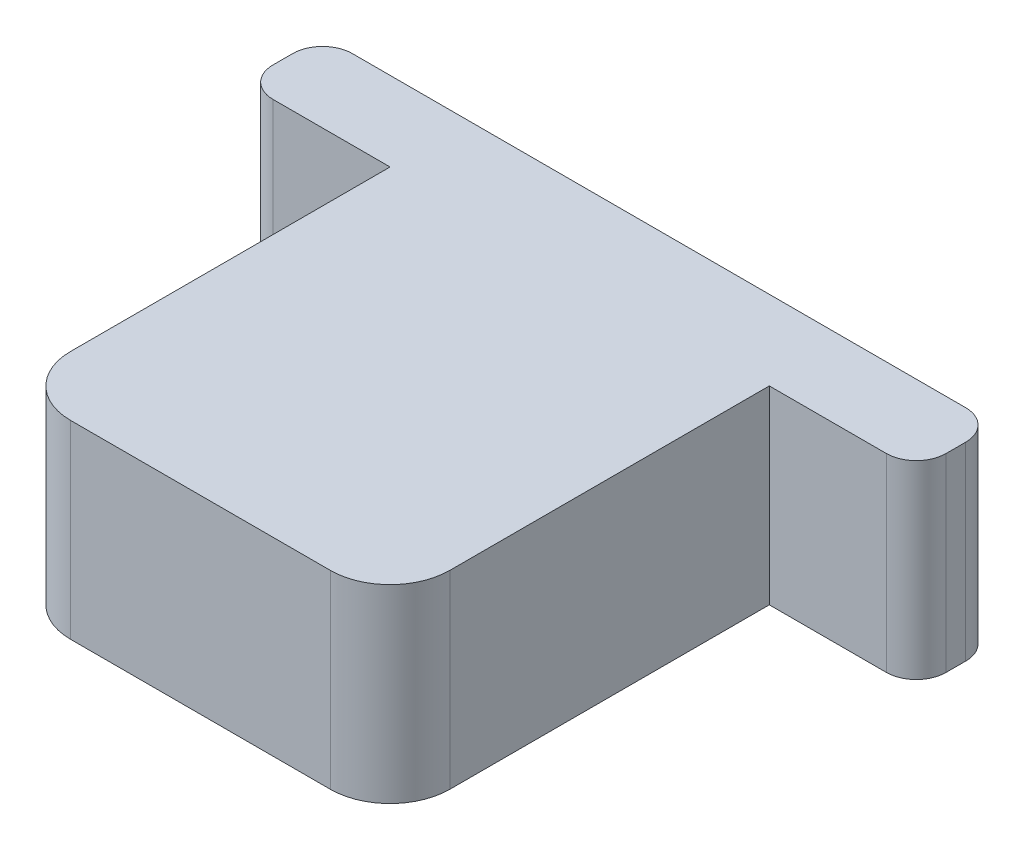
SolidWorks part; units mm, degrees
material "Beech"
ref_plane "Front Plane" through (0, 0, 0) normal (0, 0, 1) x (1, 0, 0)
ref_plane "Top Plane" through (0, 0, 0) normal (0, 1, 0) x (1, 0, 0)
ref_plane "Right Plane" through (0, 0, 0) normal (1, 0, 0) x (0, 0, -1)
sketch "Sketch1" plane through (0, 0, 0) normal (0, 1, 0) x (1, 0, 0)
  line L0 (0, 0) -> (6.35, 0)
  line L1 (0, 0) -> (0, 6.35)
  line L2 (6.35, 0) -> (6.35, 6.35)
  line L4 (-2.46, 7.6787) -> (-2.46, 6.35)
  line L5 (-2.46, 7.6787) -> (8.81, 7.6787)
  line L6 (-2.46, 6.35) -> (0, 6.35)
  line L7 (8.81, 7.6787) -> (8.81, 6.35)
  line L8 (6.35, 6.35) -> (8.81, 6.35)
  dimension "D1" = 6.35
  dimension "D2" = 6.35
  dimension "D3" = 11.27
  dimension "D4" = 1.3287
extrude "Boss-Extrude1" add sketch "Sketch1" along normal blind 3.175
fillet "Fillet1" radius 1 2 edges at (0, 1.5875, 0) (6.35, 1.5875, 0)
fillet "Fillet2" radius 0.5 4 edges at (-2.46, 1.5875, -6.35) (-2.46, 1.5875, -7.6787) (8.81, 1.5875, -7.6787) (8.81, 1.5875, -6.35)
equation "\"CageLeftBottomEdge\"=22.11mm"
equation "\"CageLeftTopEdge\"=22.11mm"
equation "\"CageRightBottomEdge\"=21.63mm"
equation "\"CageRightTopEdge\"=21.63mm"
equation "\"CageHeight\"=86.04mm"
equation "\"CageLength\"=73.76mm"
equation "\"CageTopScrewClearance\"=10mm"
equation "\"CageBottomScrewClearance\"=25mm"
equation "\"CageLeftTopDepth\"= 11.65mm"
equation "\"CageLeftBottomDepth\"=11.11mm"
equation "\"CageLeftTopHeight\"=8.56175mm"
equation "\"CageLeftBottomHeight\"=16mm"
equation "\"CageRightTopDepth\"= 11.05mm"
equation "\"CageRightBottomDepth\"=10.58mm"
equation "\"CageRightTopHeight\"=9.6mm"
equation "\"CageRightBottomHeight\"=15.49mm"
equation "\"CageLeftTopChannelDepth\"=2.41908mm"
equation "\"CageLeftBottomChannelDepth\"=2.588mm"
equation "\"CageLeftChannelHeight\"=11.7mm"
equation "\"CageRightTopChannelDepth\"=2.32mm"
equation "\"CageRightBottomChannelDepth\"=2.318mm"
equation "\"CageRightChannelHeight\"=10mm"
equation "\"CageChanRelHeight\"=23.99mm"
equation "\"CageChanRelDepth\"=5.492mm"
equation "\"CageChamberRadius\"=16.261mm"
equation "\"CageScrewDiameter\"=4.8mm"
equation "\"CageSetScrewDiameter\"=3.5mm"
equation "\"CageAxleRadius\"=6.639mm"
equation "\"CageAxleKeyHeight\"=1.619mm"
equation "\"CageAxleKeyWidth\"=2.662mm"
equation "\"CageHoseWindowWidth\"=16.29mm"
equation "\"CageHoseWindowHeight\"=26.5mm"
equation "\"CageHoseWindow-Edge\"=8.89mm"
equation "\"CageScrew-VerticalEdge\"=5.0mm"
equation "\"CageScrew-HorizontalEdge\"=7.5mm"
equation "\"CageScrew-HoseCornerScrewEdge\"=4.45mm"
equation "\"CageAxle-BottomEdge\"=56.05mm"
equation "\"CageAxle-FrontEdge\"=46.03mm"
equation "\"CageBackSetScrew-Axle\"=40mm"
equation "\"CageFrontSetScrew-Axle\"=22mm"
equation "\"CageVelocityWindow-BackEdge\"=34.8mm"
equation "\"CageVelocityWindow-BottomEdge\"=27.55mm"
equation "\"CageVelocityWindowHeight\"=22.29mm"
equation "\"CageVelocityWindowWidth\"=12.61mm"
equation "\"TriggerSlot-BottomEdge\"=6.35mm"
equation "\"TriggerSlot-FrontEdge\"=15mm"
equation "\"TriggerSlotSize\"=6.7mm"
equation "\"vigorwidth\"= 0.472441in"
equation "\"vigorflangewidth\"= 0.731102in"
equation "\"vigorflangelength\"= 0.131102in"
equation "\"vigorscrewsize\"= 0.066535in"
equation "\"vigorholeoffsetwid\"= 0.0646653in"
equation "\"vigorholeoffsetlen\"= 0.065551in"
equation "\"vigorflangedepth\"= 0.0901575in"
equation "\"vigordiscdepth\"= 0.0492126in"
equation "\"vigormotordepth\"= 1.12362in"
equation "\"vigortipdepth\"= 0.259055in"
equation "\"vigoraxlewidth\"= 0.173622in"
equation "\"vigorcutlen\"= 0.0480315in"
equation "\"vigoraxledepth\"= 0.159055in"
equation "\"TriggerRackOffset\"=.236224in"
equation "\"TriggerSlotSizeInt\"=.25in"
equation "\"MotorMountLegLength\"=.25in"
equation "\"GearOffset\"=.264907in"
equation "\"TriggerSlotSpacing\"=.25in"
equation "\"TGMGearFaceDiameter\"=24.40mm"
equation "\"TGMCylinderLength\"=15.00mm"
equation "\"TGMScrewHole-Center\"=8.70mm"
equation "\"TGMScrewHoleDiameter\"=5.04mm"
equation "\"TGMCenterHoleDiameter\"=9.50mm"
equation "\"TGMShaftCollarSideLength\"=19.00mm"
equation "\"TGMShaftCollarDockingDepth\"=7.00mm"
equation "\"whitemotordepth\"=11.27mm"
equation "\"whitemotorbackdepth\"=3.845mm"
equation "\"whitemotoraxledepth\" = 3.5mm"
equation "\"whitemotoraxleoffset\"=11.4mm"
equation "\"whitemotorwidth\"=12.07mm"
equation "\"whitemotorheight\"=16.68mm"
equation "\"whitemotorcylinderlength\" =13.04mm"
equation "\"whitemotorcylinderradius\"=3.845mm"
equation "\"whitemotorcylinderoffset\"=2.35mm"
equation "\"whitemotorcutoutlength\"=1.88mm"
equation "\"whitemotorouterrad\"=5mm"
equation "\"whitemotorinnerrad\"=2.95mm"
equation "\"D1@Sketch1\"=\"TriggerSlotSizeInt\""
equation "\"D2@Sketch1\"=\"MotorMountLegLength\""
equation "\"D3@Sketch1\"=\"whitemotordepth\""
equation "\"D4@Sketch1\"=\"GearOffset\"+\"TriggerRackOffset\"-\"whitemotoraxleoffset\""
equation "\"D1@Boss-Extrude1\"=.125in"
